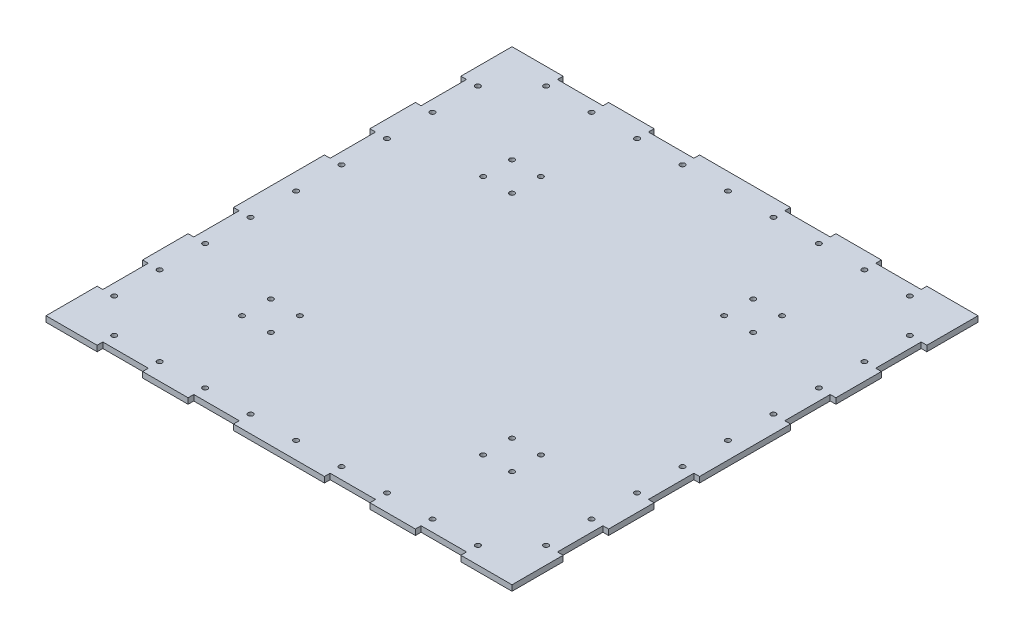
SolidWorks part; units mm, degrees
ref_plane "前视基准面" through (0, 0, 0) normal (0, 0, 1) x (1, 0, 0)
ref_plane "上视基准面" through (0, 0, 0) normal (0, 1, 0) x (1, 0, 0)
ref_plane "右视基准面" through (0, 0, 0) normal (1, 0, 0) x (0, 0, -1)
sketch "草图1" plane through (0, 0, 0) normal (0, 1, 0) x (1, 0, 0)
  line L2 (40, 200) -> (80, 200)
  line L3 (200, 40) -> (200, 80)
  line L5 (200, -40) -> (200, -80)
  line L6 (120, -200) -> (160, -200)
  line L9 (-40, -200) -> (-80, -200)
  line L10 (-200, -40) -> (-200, -80)
  line L13 (-200, 40) -> (-200, 80)
  line L14 (-40, 200) -> (-80, 200)
  line L17 (200, 205) -> (205, 205)
  line L18 (205, 200) -> (205, 205)
  line L21 (205, -200) -> (205, -205)
  line L22 (200, -205) -> (205, -205)
  line L25 (-200, -205) -> (-205, -205)
  line L26 (-205, -200) -> (-205, -205)
  line L29 (-205, 200) -> (-205, 205)
  line L30 (-200, 205) -> (-205, 205)
  line L31 (-200, 205) -> (-160, 205)
  line L32 (-160, 205) -> (-160, 200)
  line L33 (-120, 200) -> (-120, 205)
  line L34 (-120, 205) -> (-80, 205)
  line L35 (-80, 205) -> (-80, 200)
  line L36 (-80, 200) -> (-40, 200)
  line L37 (-40, 200) -> (-40, 205)
  line L38 (-40, 205) -> (40, 205)
  line L39 (40, 205) -> (40, 200)
  line L40 (80, 200) -> (80, 205)
  line L41 (80, 205) -> (120, 205)
  line L42 (120, 205) -> (120, 200)
  line L43 (120, 200) -> (160, 200)
  line L44 (160, 200) -> (160, 205)
  line L45 (160, 205) -> (200, 205)
  line L46 (205, 160) -> (200, 160)
  line L47 (200, 120) -> (205, 120)
  line L48 (205, 120) -> (205, 80)
  line L49 (205, 80) -> (200, 80)
  line L50 (200, 80) -> (200, 40)
  line L51 (200, 40) -> (205, 40)
  line L52 (205, 40) -> (205, -40)
  line L53 (205, -40) -> (200, -40)
  line L54 (200, -80) -> (205, -80)
  line L55 (205, -80) -> (205, -120)
  line L56 (205, -120) -> (200, -120)
  line L57 (200, -120) -> (200, -160)
  line L58 (200, -160) -> (205, -160)
  line L59 (205, 200) -> (205, 160)
  line L60 (205, -160) -> (205, -200)
  line L61 (160, -205) -> (160, -200)
  line L62 (120, -200) -> (120, -205)
  line L63 (120, -205) -> (80, -205)
  line L64 (80, -205) -> (80, -200)
  line L65 (80, -200) -> (40, -200)
  line L66 (40, -200) -> (40, -205)
  line L67 (40, -205) -> (-40, -205)
  line L68 (-40, -205) -> (-40, -200)
  line L69 (-80, -200) -> (-80, -205)
  line L70 (-80, -205) -> (-120, -205)
  line L71 (-120, -205) -> (-120, -200)
  line L72 (-120, -200) -> (-160, -200)
  line L73 (-160, -200) -> (-160, -205)
  line L74 (200, -205) -> (160, -205)
  line L75 (-160, -205) -> (-200, -205)
  line L76 (-205, -160) -> (-200, -160)
  line L77 (-200, -120) -> (-205, -120)
  line L78 (-205, -120) -> (-205, -80)
  line L79 (-205, -80) -> (-200, -80)
  line L80 (-200, -80) -> (-200, -40)
  line L81 (-200, -40) -> (-205, -40)
  line L82 (-205, -40) -> (-205, 40)
  line L83 (-205, 40) -> (-200, 40)
  line L84 (-200, 80) -> (-205, 80)
  line L85 (-205, 80) -> (-205, 120)
  line L86 (-205, 120) -> (-200, 120)
  line L87 (-200, 120) -> (-200, 160)
  line L88 (-200, 160) -> (-205, 160)
  line L89 (-205, -200) -> (-205, -160)
  line L90 (-205, 160) -> (-205, 200)
  line L91 (-120, 200) -> (-160, 200)
  line L92 (-200, 120) -> (-200, 160)
  line L93 (-200, -120) -> (-200, -160)
  line L94 (200, -120) -> (200, -160)
  line L95 (200, 120) -> (200, 160)
  line L96 (120, 200) -> (160, 200)
  circle A0 centre (-190, 0) radius 2.2
  circle A1 centre (-190, 40) radius 2.2
  circle A2 centre (-190, 80) radius 2.2
  circle A3 centre (-190, 120) radius 2.2
  circle A4 centre (-190, 160) radius 2.2
  circle A5 centre (-190, -160) radius 2.2
  circle A6 centre (-190, -120) radius 2.2
  circle A7 centre (-190, -80) radius 2.2
  circle A8 centre (-190, -40) radius 2.2
  circle A9 centre (0, 190) radius 2.2
  circle A10 centre (40, 190) radius 2.2
  circle A11 centre (80, 190) radius 2.2
  circle A12 centre (120, 190) radius 2.2
  circle A13 centre (160, 190) radius 2.2
  circle A14 centre (-160, 190) radius 2.2
  circle A15 centre (-120, 190) radius 2.2
  circle A16 centre (-80, 190) radius 2.2
  circle A17 centre (-40, 190) radius 2.2
  circle A18 centre (190, 0) radius 2.2
  circle A19 centre (190, -40) radius 2.2
  circle A20 centre (190, -80) radius 2.2
  circle A21 centre (190, -120) radius 2.2
  circle A22 centre (190, -160) radius 2.2
  circle A23 centre (190, 160) radius 2.2
  circle A24 centre (190, 120) radius 2.2
  circle A25 centre (190, 80) radius 2.2
  circle A26 centre (190, 40) radius 2.2
  circle A27 centre (0, -190) radius 2.2
  circle A28 centre (-40, -190) radius 2.2
  circle A29 centre (-80, -190) radius 2.2
  circle A30 centre (-120, -190) radius 2.2
  circle A31 centre (-160, -190) radius 2.2
  circle A32 centre (160, -190) radius 2.2
  circle A33 centre (120, -190) radius 2.2
  circle A34 centre (80, -190) radius 2.2
  circle A35 centre (40, -190) radius 2.2
  point P83 (0, 0)
  point P99 (0, 0)
  point P170 (0, 0)
extrude "凸台-拉伸1" add sketch "草图1" along normal blind 5 contours L47 L95 L46 L59 L18 L17 L45 L44 L43 L42 L41 L40 L2 L39 L38 L37 L14 L35 L34 L33 L91 L32 L31 L30 L29 L90 L88 L87 L86 L85 L84 L13 L83 L82 L81 L10 L79 L78 L77 L93 L76 L89 L26 L25 L75 L73 L72 L71 L70 L69 L9 region at (0, 0, 0)
sketch "草图2" plane through (0, 5, 0) normal (0, 1, 0) x (1, 0, 0)
  circle A0 centre (-118.7939, 118.7939) radius 2.2
  circle A1 centre (-93.3381, 118.7939) radius 2.2
  circle A2 centre (-93.3381, 93.3381) radius 2.2
  circle A3 centre (-118.7939, 93.3381) radius 2.2
  circle A4 centre (118.7939, 118.7939) radius 2.2
  circle A5 centre (118.7939, 93.3381) radius 2.2
  circle A6 centre (93.3381, 93.3381) radius 2.2
  circle A7 centre (93.3381, 118.7939) radius 2.2
  circle A8 centre (118.7939, -118.7939) radius 2.2
  circle A9 centre (93.3381, -118.7939) radius 2.2
  circle A10 centre (93.3381, -93.3381) radius 2.2
  circle A11 centre (118.7939, -93.3381) radius 2.2
  circle A12 centre (-118.7939, -118.7939) radius 2.2
  circle A13 centre (-118.7939, -93.3381) radius 2.2
  circle A14 centre (-93.3381, -93.3381) radius 2.2
  circle A15 centre (-93.3381, -118.7939) radius 2.2
  point P1 (0, 0)
  point P39 (0, 0)
extrude "切除-拉伸1" cut sketch "草图2" against normal blind 10
